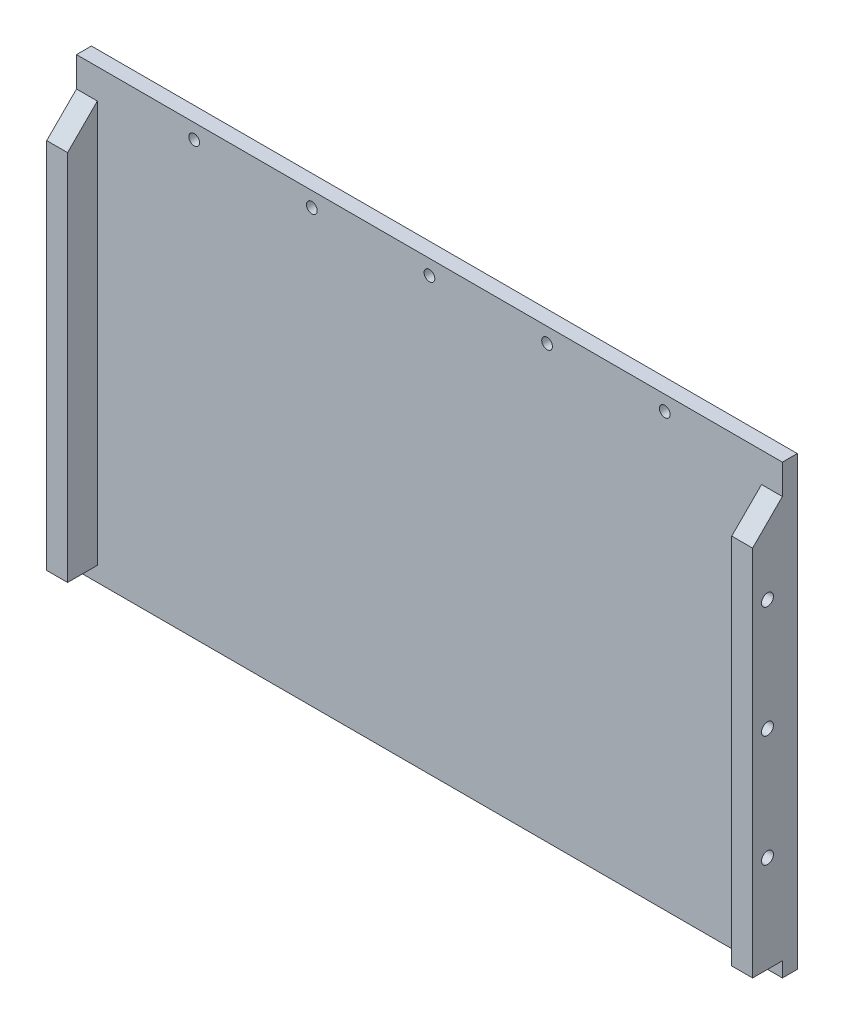
SolidWorks part; units mm, degrees
ref_plane "Płaszczyzna przednia" through (0, 0, 0) normal (0, 0, 1) x (1, 0, 0)
ref_plane "Płaszczyzna górna" through (0, 0, 0) normal (0, 1, 0) x (1, 0, 0)
ref_plane "Płaszczyzna prawa" through (0, 0, 0) normal (1, 0, 0) x (0, 0, -1)
sketch "Szkic1" plane through (0, 0, 0) normal (0, 0, 1) x (1, 0, 0)
  line L1 (-118.5, -75) -> (118.5, -75)
  line L2 (-118.5, -75) -> (-118.5, 75)
  line L3 (-118.5, 75) -> (118.5, 75)
  line L4 (118.5, -75) -> (118.5, 75)
  line L5 (0, 75) -> (0, -75) construction
  line L6 (-118.5, 0) -> (118.5, 0) construction
  point P0 (0, 0)
  dimension "D1" = 237
  dimension "D2" = 150
extrude "Dodanie-wyciągnięcie1" add sketch "Szkic1" along normal blind 5
sketch "Szkic2" plane through (0, 0, 5) normal (0, 0, 1) x (1, 0, 0)
  line L0 (118.5, -75) -> (118.5, 75) construction
  line L1 (118.5, 65) -> (111.5, 65)
  line L2 (118.5, 65) -> (118.5, -70)
  line L3 (118.5, -70) -> (111.5, -70)
  line L4 (111.5, 65) -> (111.5, -70)
  line L5 (115, -70) -> (115, 65) construction
  line L6 (118.5, -2.5) -> (111.5, -2.5) construction
  line L7 (118.5, 75) -> (-118.5, 75) construction
  line L8 (-118.5, -75) -> (118.5, -75) construction
  line L9 (0, 0) -> (0, 75) construction
  line L10 (-118.5, -2.5) -> (-111.5, -2.5) construction
  line L11 (-115, -70) -> (-115, 65) construction
  line L12 (-111.5, 65) -> (-111.5, -70)
  line L13 (-118.5, -70) -> (-111.5, -70)
  line L14 (-118.5, 65) -> (-118.5, -70)
  line L15 (-118.5, 65) -> (-111.5, 65)
  point P20 (-115, -2.5)
  point P300 (115, -2.5)
  dimension "D1" = 10
  dimension "D2" = 5
  dimension "D3" = 7
extrude "Dodanie-wyciągnięcie2" add sketch "Szkic2" along normal blind 10
sketch "Szkic3" plane through (118.5, 0, 0) normal (1, 0, 0) x (0, 0, -1)
  line L0 (-10, 65) -> (-10, -70) construction
  line L1 (-15, 65) -> (-5, 65) construction
  line L2 (-15, -70) -> (-5, -70) construction
  line L3 (0, 0) -> (-15, 0) construction
  line L4 (0, -75) -> (0, 75) construction
  line L5 (-15, -70) -> (-15, 65) construction
  point P6 (-10, 37.5)
  point P7 (-10, 0)
  point P8 (-10, -37.5)
  point P9 (0, 0)
  dimension "D1" = 37.5
hole_wizard "Otwór Ø4.0 (4)1" positions "Szkic3" profile "Szkic4" hole size "Ø4.0" standard "DIN"
sketch "Szkic4" plane through (118.5, -37.5, 10) normal (0, 1, 0) x (0, 0, -1)
  line L0 (0, 0) -> (0, 6.7)
  line L1 (0, 6.7) -> (2, 6.7)
  line L2 (2, 6.7) -> (2, 0)
  line L5 (2, 0) -> (0, 0)
  line L10 (0, 6.7) -> (-2, 6.7) construction
  line L11 (0, -6.35) -> (0, 107.95) construction
  dimension "Średnica otworu" = 4
  dimension "Głębokość otworu" = 6.7
  dimension "Kąt wiertła" = 180
ref_plane "Płaszczyzna1" through (0, 0, 0) normal (-1, 0, 0) x (0, 0, 1)
mirror "Lustro1" about plane through (0, 0, 0) normal (-1, 0, 0) of "Otwór Ø4.0 (4)1"
chamfer "Sfazowanie1" distance 10 angle 45 2 edges at (-115, 65, 15) (115, 65, 15)
sketch "Szkic11" plane through (0, 0, 0) normal (0, 0, -1) x (-1, 0, 0)
  line L0 (-118.5, -75) -> (-118.5, 75) construction
  line L1 (-118.5, 75) -> (118.5, 75) construction
  point P0 (-79, 70)
  point P5 (-39.5, 70)
  point P6 (79, 70)
  point P7 (0, 70)
  point P8 (39.5, 70)
  point P10 (-31.065, 74.0224)
  dimension "D1" = 39.5
  dimension "D2" = 5
  dimension "D4" = 39.5
  dimension "D3" = 5
hole_wizard "Pogłębienie walcowe pod M3 Śrubę z łbem stożkowym ściętym1" positions "Szkic11" profile "Szkic12" counterbore size "M3" standard "DIN"
sketch "Szkic12" plane through (79, 70, 0) normal (1, 0, 0) x (0, 1, 0)
  line L0 (0, 0) -> (0, 7.7815)
  line L1 (0, 7.7815) -> (1.8, 6.7)
  line L2 (1.8, 6.7) -> (1.8, 2.4)
  line L3 (1.8, 2.4) -> (3.5, 2.4)
  line L4 (3.5, 2.4) -> (3.5, 0)
  line L5 (3.5, 0) -> (0, 0)
  line L10 (0, 7.7815) -> (-1.8, 6.7) construction
  line L11 (0, -6.35) -> (0, 107.95) construction
  dimension "Średnica otworu" = 3.6
  dimension "Głębokość otworu" = 6.7
  dimension "Średnica pogłębienia walcowego" = 7
  dimension "Głębokość pogłębienia walcowego" = 2.4
  dimension "Kąt wiertła" = 118
sketch "Szkic13" plane through (0, -70, 0) normal (0, -1, 0) x (1, 0, 0)
  line L0 (-118.5, 15) -> (-111.5, 5) construction
  line L1 (111.5, 5) -> (118.5, 15) construction
  point P8 (-115, 10)
  point P9 (115, 10)
hole_wizard "Otwory ustalające Ø4.0mm1" positions "Szkic13" profile "Szkic14" hole size "Ø4.0" standard "DIN"
sketch "Szkic14" plane through (115, -70, 10) normal (1, 0, 0) x (0, 0, -1)
  line L0 (0, 0) -> (0, 6.7)
  line L1 (0, 6.7) -> (2, 6.7)
  line L2 (2, 6.7) -> (2, 0)
  line L5 (2, 0) -> (0, 0)
  line L10 (0, 6.7) -> (-2, 6.7) construction
  line L11 (0, -6.35) -> (0, 107.95) construction
  dimension "Średnica otworu" = 4
  dimension "Głębokość otworu" = 6.7
  dimension "Kąt wiertła" = 180
